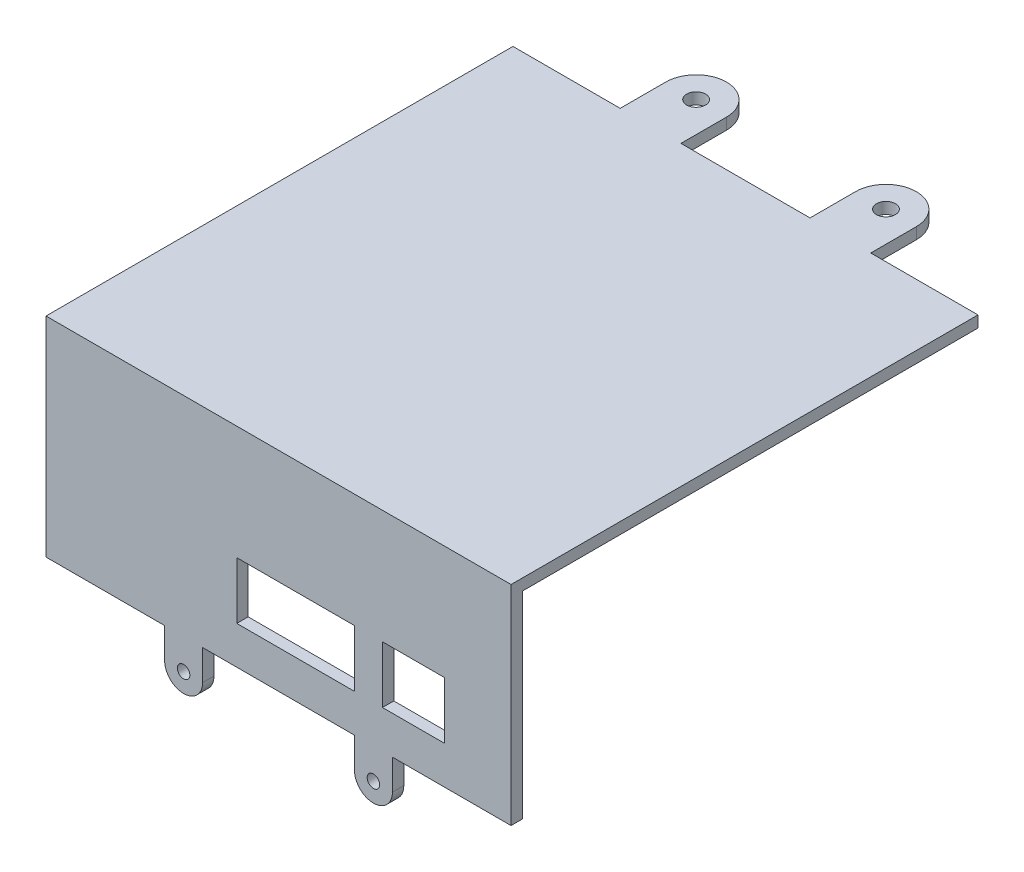
SolidWorks part; units mm, degrees
ref_plane "前视基准面" through (0, 0, 0) normal (0, 0, 1) x (1, 0, 0)
ref_plane "上视基准面" through (0, 0, 0) normal (0, 1, 0) x (1, 0, 0)
ref_plane "右视基准面" through (0, 0, 0) normal (1, 0, 0) x (0, 0, -1)
sketch "草图1" plane through (0, 0, 0) normal (0, 1, 0) x (1, 0, 0)
  line L1 (61.25, -60) -> (-61.25, -60)
  line L2 (61.25, -60) -> (61.25, 60)
  line L3 (61.25, 60) -> (-61.25, 60)
  line L4 (-61.25, -60) -> (-61.25, 60)
  line L5 (61.25, -60) -> (-61.25, 60) construction
  line L6 (61.25, 60) -> (-61.25, -60) construction
  circle A0 centre (0, 0) radius 5 construction
  point P0 (0, 0)
  dimension "D1" = 120
  dimension "D2" = 122.5
  dimension "D3" = 61.25
extrude "凸台-拉伸1" add sketch "草图1" along normal blind 3
ref_plane "基准面1" through (0, 3, 0) normal (0, 1, 0) x (1, 0, 0)
ref_plane "基准面2" through (0, 0, 0) normal (1, 0, 0) x (0, 0, -1)
sketch "草图5" plane through (0, 0, 0) normal (1, 0, 0) x (0, 0, -1)
  line L0 (66, 3) -> (-66, 3) construction
  line L1 (-60, -52) -> (-63, -52)
  line L2 (-60, -52) -> (-60, 3)
  line L3 (-60, 3) -> (-63, 3)
  line L4 (-63, -52) -> (-63, 3)
  dimension "D1" = 3
  dimension "D2" = 55
extrude "凸台-拉伸2" add sketch "草图5" along normal blind 61.25 and the other way blind 61.25
ref_plane "基准面4" through (61.25, 0, 0) normal (1, 0, 0) x (0, 0, -1)
ref_plane "基准面6" through (0, 0, 1.5) normal (0, 0, 1) x (1, 0, 0)
ref_plane "基准面7" through (0, 0, -56) normal (0, 0, -1) x (-1, 0, 0)
ref_plane "基准面8" through (0, 0, 63) normal (0, 0, 1) x (1, 0, 0)
sketch "草图23" plane through (0, 3, 0) normal (0, 1, 0) x (1, 0, 0)
  line L0 (61.25, 60) -> (-61.25, 60) construction
  line L1 (17, 60) -> (33, 60)
  line L2 (17, 60) -> (17, 72)
  line L4 (33, 60) -> (33, 72)
  line L10 (33, 72) -> (17, 72) construction
  line L11 (0, -1.65) -> (0, 1.65) construction
  line L12 (-17, 60) -> (-17, 72)
  line L13 (-17, 60) -> (-33, 60)
  line L14 (-33, 60) -> (-33, 72)
  arc A2 (17, 72) -> (33, 72) centre (25, 72) cw
  arc A3 (-17, 72) -> (-33, 72) centre (-25, 72) ccw
  dimension "D1" = 16
  dimension "D2" = 12
  dimension "D3" = 25
extrude "凸台-拉伸3" add sketch "草图23" against normal blind 3
hole_wizard "M6 螺纹孔1" positions "草图24" profile "草图25" tap size "M6" standard "GB" end condition through all
sketch "草图24" plane through (0, 3, 0) normal (0, 1, 0) x (1, 0, 0)
  line L3 (17, 72) -> (17, 60) construction
  line L4 (61.25, 60) -> (33, 60) construction
  line L5 (-33, 60) -> (-61.25, 60) construction
  point P0 (-25, 72)
  point P2 (25, 72)
  dimension "D3" = 8
  dimension "D1" = 12
  dimension "D2" = 12
sketch "草图25" plane through (-25, 3, -72) normal (1, 0, 0) x (0, 0, 1)
  line L0 (0, 0) -> (0, 55)
  line L1 (0, 55) -> (2.5, 55)
  line L2 (2.5, 55) -> (2.5, 0)
  line L5 (2.5, 0) -> (0, 0)
  line L11 (0, -6.35) -> (0, 107.95) construction
  dimension "通孔螺纹孔钻头直径" = 5
  dimension "通孔螺纹孔钻头深度" = 55
cosmetic thread "孔螺蚊线17" parameters "D2"=6
cosmetic thread "孔螺蚊线18" parameters "D2"=6
sketch "草图26" plane through (0, 0, 63) normal (0, 0, 1) x (1, 0, 0)
  line L0 (-61.25, -52) -> (61.25, -52) construction
  line L1 (-30, -52) -> (-20, -52)
  line L2 (-30, -52) -> (-30, -60)
  line L4 (-20, -52) -> (-20, -60)
  line L9 (-30, -60) -> (-20, -60) construction
  line L10 (0, -30.25) -> (0, 30.25) construction
  line L11 (30, -52) -> (20, -52)
  line L12 (30, -52) -> (30, -60)
  line L13 (20, -52) -> (20, -60)
  arc A2 (-30, -60) -> (-20, -60) centre (-25, -60) ccw
  arc A3 (30, -60) -> (20, -60) centre (25, -60) cw
  dimension "D1" = 10
  dimension "D2" = 8
  dimension "D3" = 25
extrude "凸台-拉伸4" add sketch "草图26" against normal blind 3
hole_wizard "M4 螺纹孔3" positions "草图27" profile "草图28" tap size "M4" standard "GB" end condition through all
sketch "草图27" plane through (0, 0, 63) normal (0, 0, 1) x (1, 0, 0)
  line L0 (-30, -52) -> (-30, -60) construction
  line L3 (-61.25, -52) -> (-30, -52) construction
  point P0 (-25, -60)
  dimension "D1" = 5
  dimension "D2" = 8
sketch "草图28" plane through (-25, -60, 63) normal (1, 0, 0) x (0, -1, 0)
  line L0 (0, 0) -> (0, 143)
  line L1 (0, 143) -> (1.65, 143)
  line L2 (1.65, 143) -> (1.65, 0)
  line L5 (1.65, 0) -> (0, 0)
  line L11 (0, -6.35) -> (0, 107.95) construction
  dimension "通孔螺纹孔钻头直径" = 3.3
  dimension "通孔螺纹孔钻头深度" = 143
cosmetic thread "孔螺蚊线20" parameters "D2"=4
mirror "镜向8" about plane through (0, 0, 0) normal (1, 0, 0) of "M4 螺纹孔3"
ref_plane "基准面9" through (0, 0, 63) normal (0, 0, 1) x (1, 0, 0)
sketch "草图29" plane through (0, 0, 63) normal (0, 0, 1) x (1, 0, 0)
  line L0 (-71.1934, -42) -> (74.4205, -42) construction
  line L1 (-61.25, -52) -> (-30, -52) construction
  line L2 (-75.1855, -27) -> (74.4205, -27) construction
  line L3 (0, -30.25) -> (0, 30.25) construction
  line L4 (-11, -27) -> (20, -27)
  line L5 (-11, -27) -> (-11, -42)
  line L6 (-11, -42) -> (20, -42)
  line L7 (20, -27) -> (20, -42)
  line L8 (27.37, -27) -> (43.67, -27)
  line L9 (27.37, -27) -> (27.37, -42)
  line L10 (27.37, -42) -> (43.67, -42)
  line L11 (43.67, -27) -> (43.67, -42)
  dimension "D1" = 10
  dimension "D2" = 25
  dimension "D3" = 31
  dimension "D4" = 11
  dimension "D5" = 16.3
  dimension "D6" = 27.37
extrude "切除-拉伸1" cut sketch "草图29" against normal through all
equation "\"D2@草图24\"=\"D1@草图24\""
